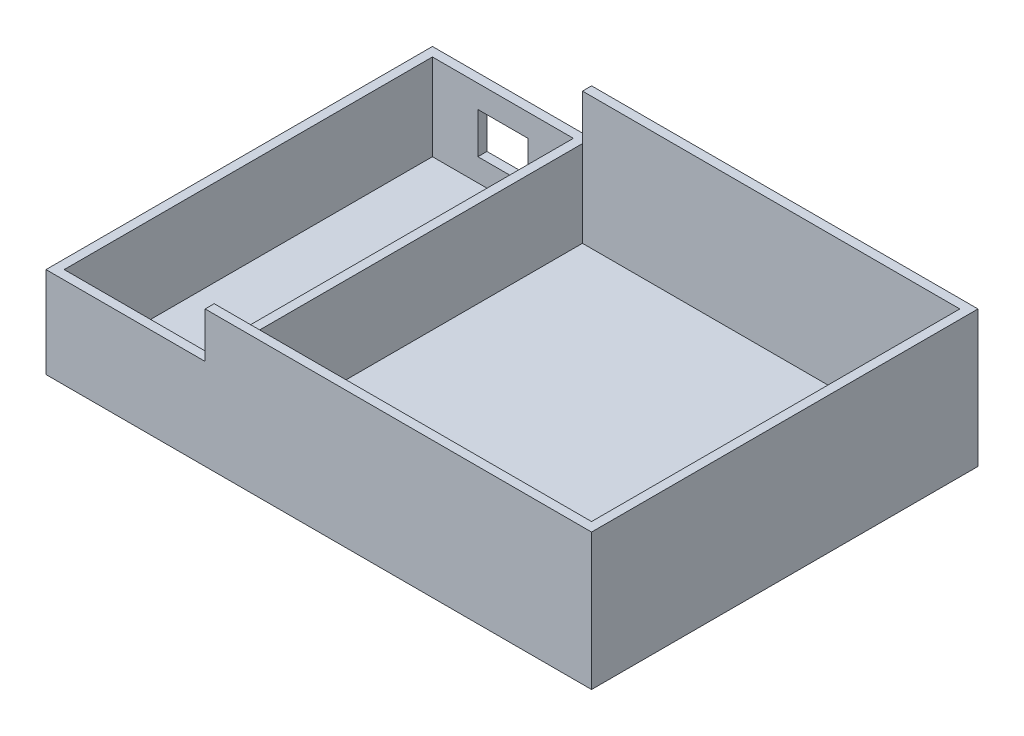
SolidWorks part; units mm, degrees
ref_plane "Front Plane" through (0, 0, 0) normal (0, 0, 1) x (1, 0, 0)
ref_plane "Top Plane" through (0, 0, 0) normal (0, 1, 0) x (1, 0, 0)
ref_plane "Right Plane" through (0, 0, 0) normal (1, 0, 0) x (0, 0, -1)
sketch "Sketch1" plane through (0, 0, 0) normal (0, 1, 0) x (1, 0, 0)
  line L1 (-60, 42.5) -> (60, 42.5)
  line L2 (-60, 42.5) -> (-60, -42.5)
  line L3 (-60, -42.5) -> (60, -42.5)
  line L4 (60, 42.5) -> (60, -42.5)
  line L5 (-60, 42.5) -> (60, -42.5) construction
  line L6 (-60, -42.5) -> (60, 42.5) construction
  point P0 (0, 0)
  dimension "D1" = 120
  dimension "D2" = 85
extrude "Boss-Extrude1" add sketch "Sketch1" along normal blind 30
sketch "Sketch2" plane through (0, 30, 0) normal (0, 1, 0) x (1, 0, 0)
  line L0 (60, 42.5) -> (-60, 42.5) construction
  line L1 (58, 40.5) -> (-25, 40.5)
  line L2 (58, 40.5) -> (58, -40.5)
  line L3 (58, -40.5) -> (-25, -40.5)
  line L4 (-25, 40.5) -> (-25, -40.5)
  line L5 (58, 40.5) -> (-25, -40.5) construction
  line L6 (58, -40.5) -> (-25, 40.5) construction
  line L7 (60, -42.5) -> (60, 42.5) construction
  dimension "D1" = 2
  dimension "D2" = 2
  dimension "D3" = 83
extrude "Cut-Extrude1" cut sketch "Sketch2" against normal blind 29
sketch "Sketch3" plane through (0, 30, 0) normal (0, 1, 0) x (1, 0, 0)
  line L0 (-60, -42.5) -> (60, -42.5) construction
  line L1 (-58, 40.5) -> (-27, 40.5)
  line L2 (-58, 40.5) -> (-58, -40.5)
  line L3 (-58, -40.5) -> (-27, -40.5)
  line L4 (-27, 40.5) -> (-27, -40.5)
  line L5 (-58, 40.5) -> (-27, -40.5) construction
  line L6 (-58, -40.5) -> (-27, 40.5) construction
  line L8 (-25, 40.5) -> (-25, -40.5) construction
  line L9 (-60, 42.5) -> (-60, -42.5) construction
  point P0 (-42.5, 0)
  dimension "D1" = 81
  dimension "D2" = 2
  dimension "D3" = 2
  dimension "D4" = 2
extrude "Cut-Extrude2" cut sketch "Sketch3" against normal blind 29
sketch "Sketch4" plane through (0, 30, 0) normal (0, 1, 0) x (1, 0, 0)
  line L0 (-60, -42.5) -> (60, -42.5) construction
  line L1 (-60, 42.5) -> (-25, 42.5)
  line L2 (-60, 42.5) -> (-60, -42.5)
  line L3 (-60, -42.5) -> (-25, -42.5)
  line L4 (-25, 42.5) -> (-25, -42.5)
extrude "Cut-Extrude3" cut sketch "Sketch4" against normal blind 10
sketch "Sketch5" plane through (0, 0, -40.5) normal (0, 0, 1) x (1, 0, 0)
  line L0 (-58, 20) -> (-27, 20) construction
  line L1 (-48, 15) -> (-37, 15)
  line L2 (-48, 15) -> (-48, 6)
  line L3 (-48, 6) -> (-37, 6)
  line L4 (-37, 15) -> (-37, 6)
  line L5 (-48, 15) -> (-37, 6) construction
  line L6 (-48, 6) -> (-37, 15) construction
  line L7 (-27, 1) -> (-58, 1) construction
  line L8 (-27, 1) -> (-27, 20) construction
  line L9 (-58, 1) -> (-58, 20) construction
  point P0 (-42.5, 10.5)
  point P9 (-27, 10.5)
  dimension "D1" = 5
  dimension "D2" = 5
  dimension "D3" = 10
  dimension "D4" = 10
extrude "Cut-Extrude4" cut sketch "Sketch5" against normal through all
